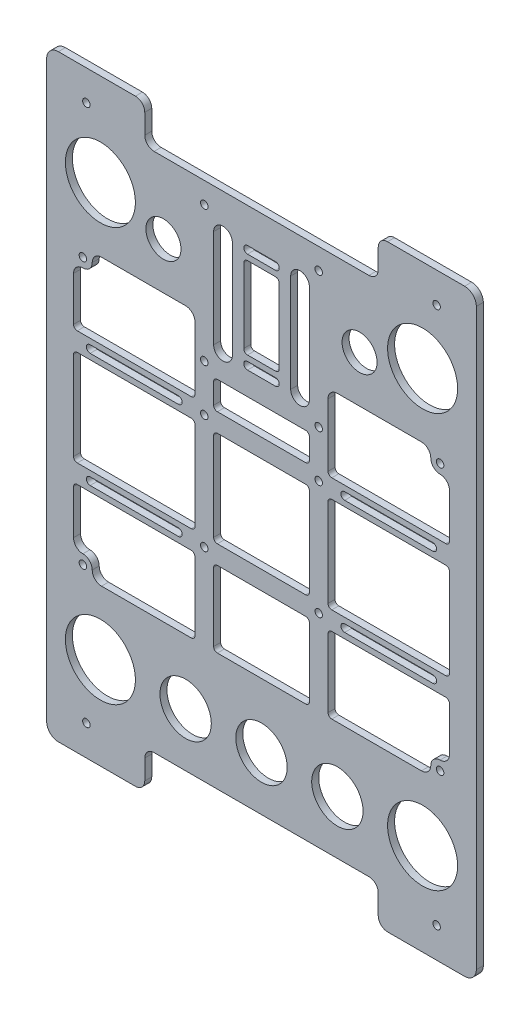
SolidWorks part; units mm, degrees
material "Thornel Mat VMA"
ref_plane "Front Plane" through (0, 0, 0) normal (0, 0, 1) x (1, 0, 0)
ref_plane "Top Plane" through (0, 0, 0) normal (0, 1, 0) x (1, 0, 0)
ref_plane "Right Plane" through (0, 0, 0) normal (1, 0, 0) x (0, 0, -1)
sketch "Model" plane through (0, 0, 0) normal (0, 0, 1) x (1, 0, 0)
  line L0 (-87, -128) -> (-54, -128)
  line L1 (54, -128) -> (87, -128)
  line L2 (92, -123) -> (92, 123)
  line L3 (-54, 128) -> (-87, 128)
  line L4 (-92, 123) -> (-92, -123)
  line L5 (-18.9, 40.5) -> (18.9, 40.5)
  line L6 (-68.5, 61) -> (-32.5, 61)
  line L7 (-80.5, 49) -> (-80.5, 30.1)
  line L8 (-80.5, 18.9) -> (-80.5, -18.9)
  line L9 (-80.5, -30.1) -> (-80.5, -49)
  line L10 (32.5, 61) -> (68.5, 61)
  line L11 (80.5, 49) -> (80.5, 30.1)
  line L12 (80.5, 18.9) -> (80.5, -18.9)
  line L13 (80.5, -30.1) -> (80.5, -49)
  line L14 (-20.5, 52.5) -> (-20.5, 94.5)
  line L15 (-12.5, 94.5) -> (-12.5, 52.5)
  line L16 (-50, 124) -> (-50, 115.5)
  line L17 (50, 115.5) -> (50, 124)
  line L18 (-46, 111.5) -> (46, 111.5)
  line L19 (54, 128) -> (87, 128)
  line L20 (-68.5, -61) -> (-30.1, -61)
  line L21 (-18.9, -61) -> (18.9, -61)
  line L22 (30.1, -61) -> (68.5, -61)
  line L23 (-50, -124) -> (-50, -115.5)
  line L24 (50, -115.5) -> (50, -124)
  line L25 (-46, -111.5) -> (46, -111.5)
  line L26 (-6, 96.6) -> (6, 96.6)
  line L27 (-6, 93.4) -> (6, 93.4)
  line L28 (-6, 53.6) -> (6, 53.6)
  line L29 (-6, 50.4) -> (6, 50.4)
  line L30 (-6, 91) -> (6, 91)
  line L31 (7.6, 89.4) -> (7.6, 57.6)
  line L32 (6, 56) -> (-6, 56)
  line L33 (-7.6, 57.6) -> (-7.6, 89.4)
  line L34 (20.5, 52.5) -> (20.5, 94.5)
  line L35 (12.5, 94.5) -> (12.5, 52.5)
  line L36 (-28.5, 57) -> (-28.5, 30.1)
  line L37 (-28.5, 18.9) -> (-28.5, -18.9)
  line L38 (-28.5, -30.1) -> (-28.5, -59.4)
  line L39 (-20.5, 38.9) -> (-20.5, 30.1)
  line L40 (-20.5, 18.9) -> (-20.5, -18.9)
  line L41 (-20.5, -30.1) -> (-20.5, -59.4)
  line L42 (28.5, 57) -> (28.5, 30.1)
  line L43 (28.5, 18.9) -> (28.5, -18.9)
  line L44 (28.5, -30.1) -> (28.5, -59.4)
  line L45 (20.5, 38.9) -> (20.5, 30.1)
  line L46 (20.5, 18.9) -> (20.5, -18.9)
  line L47 (20.5, -30.1) -> (20.5, -59.4)
  line L48 (-78.9, -20.5) -> (-30.1, -20.5)
  line L49 (-18.9, -20.5) -> (18.9, -20.5)
  line L50 (30.1, -20.5) -> (78.9, -20.5)
  line L51 (-78.9, -28.5) -> (-30.1, -28.5)
  line L52 (-18.9, -28.5) -> (18.9, -28.5)
  line L53 (30.1, -28.5) -> (78.9, -28.5)
  line L54 (-78.9, 20.5) -> (-30.1, 20.5)
  line L55 (-18.9, 20.5) -> (18.9, 20.5)
  line L56 (30.1, 20.5) -> (78.9, 20.5)
  line L57 (-78.9, 28.5) -> (-30.1, 28.5)
  line L58 (-18.9, 28.5) -> (18.9, 28.5)
  line L59 (30.1, 28.5) -> (78.9, 28.5)
  line L60 (-73.4, 26.1) -> (-35.6, 26.1)
  line L61 (-73.4, 22.9) -> (-35.6, 22.9)
  line L62 (-73.4, -26.1) -> (-35.6, -26.1)
  line L63 (-73.4, -22.9) -> (-35.6, -22.9)
  line L64 (35.6, 26.1) -> (73.4, 26.1)
  line L65 (35.6, 22.9) -> (73.4, 22.9)
  line L66 (35.6, -26.1) -> (73.4, -26.1)
  line L67 (35.6, -22.9) -> (73.4, -22.9)
  circle A0 centre (-75, 115) radius 1.6
  circle A1 centre (75, 115) radius 1.6
  circle A2 centre (-75, -115) radius 1.6
  circle A3 centre (75, -115) radius 1.6
  circle A4 centre (-69, 88.5) radius 15
  circle A5 centre (69, 88.5) radius 15
  circle A6 centre (-69, -88.5) radius 15
  circle A7 centre (69, -88.5) radius 15
  arc A8 (87, -128) -> (92, -123) centre (87, -123) ccw
  arc A9 (92, 123) -> (87, 128) centre (87, 123) ccw
  arc A10 (-50, 124) -> (-54, 128) centre (-54, 124) ccw
  arc A11 (-92, -123) -> (-87, -128) centre (-87, -123) ccw
  arc A12 (-87, 128) -> (-92, 123) centre (-87, 123) ccw
  circle A13 centre (-24.5, 44.5) radius 1.6
  circle A14 centre (24.5, 44.5) radius 1.6
  circle A15 centre (-24.5, 102.5) radius 1.6
  circle A16 centre (24.5, 102.5) radius 1.6
  circle A17 centre (0, -88.5) radius 11
  circle A18 centre (-76.5, -57) radius 1.6
  circle A19 centre (-76.5, 57) radius 1.6
  circle A20 centre (76.5, -57) radius 1.6
  circle A21 centre (76.5, 57) radius 1.6
  circle A22 centre (-32.5, -88.5) radius 11
  circle A23 centre (32.5, -88.5) radius 11
  arc A24 (-76.5, 53) -> (-72.5, 57) centre (-76.5, 57) ccw
  arc A25 (20.5, 38.9) -> (18.9, 40.5) centre (18.9, 38.9) ccw
  arc A26 (-72.5, -57) -> (-76.5, -53) centre (-76.5, -57) ccw
  arc A27 (76.5, -53) -> (72.5, -57) centre (76.5, -57) ccw
  arc A28 (72.5, 57) -> (76.5, 53) centre (76.5, 57) ccw
  arc A29 (-28.5, 57) -> (-32.5, 61) centre (-32.5, 57) ccw
  arc A30 (-68.5, 61) -> (-72.5, 57) centre (-68.5, 57) ccw
  arc A31 (-80.5, 30.1) -> (-78.9, 28.5) centre (-78.9, 30.1) ccw
  arc A32 (-78.9, 20.5) -> (-80.5, 18.9) centre (-78.9, 18.9) ccw
  arc A33 (-80.5, -18.9) -> (-78.9, -20.5) centre (-78.9, -18.9) ccw
  arc A34 (-78.9, -28.5) -> (-80.5, -30.1) centre (-78.9, -30.1) ccw
  arc A35 (-80.5, -49) -> (-76.5, -53) centre (-76.5, -49) ccw
  arc A36 (-76.5, 53) -> (-80.5, 49) centre (-76.5, 49) ccw
  arc A37 (68.5, -61) -> (72.5, -57) centre (68.5, -57) ccw
  arc A38 (-72.5, -57) -> (-68.5, -61) centre (-68.5, -57) ccw
  arc A39 (32.5, 61) -> (28.5, 57) centre (32.5, 57) ccw
  arc A40 (72.5, 57) -> (68.5, 61) centre (68.5, 57) ccw
  arc A41 (78.9, 28.5) -> (80.5, 30.1) centre (78.9, 30.1) ccw
  arc A42 (78.9, -20.5) -> (80.5, -18.9) centre (78.9, -18.9) ccw
  arc A43 (76.5, -53) -> (80.5, -49) centre (76.5, -49) ccw
  arc A44 (80.5, 49) -> (76.5, 53) centre (76.5, 49) ccw
  arc A45 (-16.5, 98.5) -> (-20.5, 94.5) centre (-16.5, 94.5) ccw
  arc A46 (-20.5, 52.5) -> (-16.5, 48.5) centre (-16.5, 52.5) ccw
  arc A47 (-12.5, 94.5) -> (-16.5, 98.5) centre (-16.5, 94.5) ccw
  arc A48 (-16.5, 48.5) -> (-12.5, 52.5) centre (-16.5, 52.5) ccw
  arc A49 (-50, 115.5) -> (-46, 111.5) centre (-46, 115.5) ccw
  arc A50 (54, 128) -> (50, 124) centre (54, 124) ccw
  arc A51 (46, 111.5) -> (50, 115.5) centre (46, 115.5) ccw
  arc A52 (-30.1, -61) -> (-28.5, -59.4) centre (-30.1, -59.4) ccw
  arc A53 (-20.5, -59.4) -> (-18.9, -61) centre (-18.9, -59.4) ccw
  circle A54 centre (-42, 81) radius 7.5
  circle A55 centre (42, 81) radius 7.5
  arc A56 (-54, -128) -> (-50, -124) centre (-54, -124) ccw
  arc A57 (-46, -111.5) -> (-50, -115.5) centre (-46, -115.5) ccw
  arc A58 (50, -124) -> (54, -128) centre (54, -124) ccw
  arc A59 (50, -115.5) -> (46, -111.5) centre (46, -115.5) ccw
  arc A60 (-6, 96.6) -> (-6, 93.4) centre (-6, 95) ccw
  arc A61 (6, 93.4) -> (6, 96.6) centre (6, 95) ccw
  arc A62 (-6, 53.6) -> (-6, 50.4) centre (-6, 52) ccw
  arc A63 (6, 50.4) -> (6, 53.6) centre (6, 52) ccw
  arc A64 (6, 56) -> (7.6, 57.6) centre (6, 57.6) ccw
  arc A65 (7.6, 89.4) -> (6, 91) centre (6, 89.4) ccw
  arc A66 (-7.6, 57.6) -> (-6, 56) centre (-6, 57.6) ccw
  arc A67 (-6, 91) -> (-7.6, 89.4) centre (-6, 89.4) ccw
  arc A68 (20.5, 94.5) -> (16.5, 98.5) centre (16.5, 94.5) ccw
  arc A69 (16.5, 48.5) -> (20.5, 52.5) centre (16.5, 52.5) ccw
  arc A70 (16.5, 98.5) -> (12.5, 94.5) centre (16.5, 94.5) ccw
  arc A71 (12.5, 52.5) -> (16.5, 48.5) centre (16.5, 52.5) ccw
  arc A72 (-18.9, 40.5) -> (-20.5, 38.9) centre (-18.9, 38.9) ccw
  arc A73 (-20.5, 30.1) -> (-18.9, 28.5) centre (-18.9, 30.1) ccw
  arc A74 (-20.5, -18.9) -> (-18.9, -20.5) centre (-18.9, -18.9) ccw
  arc A75 (-18.9, 20.5) -> (-20.5, 18.9) centre (-18.9, 18.9) ccw
  arc A76 (-18.9, -28.5) -> (-20.5, -30.1) centre (-18.9, -30.1) ccw
  arc A77 (28.5, 30.1) -> (30.1, 28.5) centre (30.1, 30.1) ccw
  arc A78 (28.5, -18.9) -> (30.1, -20.5) centre (30.1, -18.9) ccw
  arc A79 (30.1, 20.5) -> (28.5, 18.9) centre (30.1, 18.9) ccw
  arc A80 (28.5, -59.4) -> (30.1, -61) centre (30.1, -59.4) ccw
  arc A81 (18.9, 28.5) -> (20.5, 30.1) centre (18.9, 30.1) ccw
  arc A82 (18.9, -61) -> (20.5, -59.4) centre (18.9, -59.4) ccw
  arc A83 (-30.1, -20.5) -> (-28.5, -18.9) centre (-30.1, -18.9) ccw
  arc A84 (18.9, -20.5) -> (20.5, -18.9) centre (18.9, -18.9) ccw
  arc A85 (-28.5, -30.1) -> (-30.1, -28.5) centre (-30.1, -30.1) ccw
  arc A86 (20.5, -30.1) -> (18.9, -28.5) centre (18.9, -30.1) ccw
  arc A87 (80.5, -30.1) -> (78.9, -28.5) centre (78.9, -30.1) ccw
  arc A88 (30.1, -28.5) -> (28.5, -30.1) centre (30.1, -30.1) ccw
  arc A89 (-28.5, 18.9) -> (-30.1, 20.5) centre (-30.1, 18.9) ccw
  arc A90 (20.5, 18.9) -> (18.9, 20.5) centre (18.9, 18.9) ccw
  arc A91 (80.5, 18.9) -> (78.9, 20.5) centre (78.9, 18.9) ccw
  arc A92 (-30.1, 28.5) -> (-28.5, 30.1) centre (-30.1, 30.1) ccw
  arc A93 (-73.4, 26.1) -> (-73.4, 22.9) centre (-73.4, 24.5) ccw
  arc A94 (-73.4, -22.9) -> (-73.4, -26.1) centre (-73.4, -24.5) ccw
  arc A95 (-35.6, 22.9) -> (-35.6, 26.1) centre (-35.6, 24.5) ccw
  arc A96 (-35.6, -26.1) -> (-35.6, -22.9) centre (-35.6, -24.5) ccw
  arc A97 (35.6, 26.1) -> (35.6, 22.9) centre (35.6, 24.5) ccw
  arc A98 (35.6, -22.9) -> (35.6, -26.1) centre (35.6, -24.5) ccw
  arc A99 (73.4, 22.9) -> (73.4, 26.1) centre (73.4, 24.5) ccw
  arc A100 (73.4, -26.1) -> (73.4, -22.9) centre (73.4, -24.5) ccw
  circle A101 centre (-24.5, 24.5) radius 1.6
  circle A102 centre (24.5, 24.5) radius 1.6
  circle A103 centre (-24.5, -24.5) radius 1.6
  circle A104 centre (24.5, -24.5) radius 1.6
extrude "Boss-Extrude1" add sketch "Model" along normal blind 3
